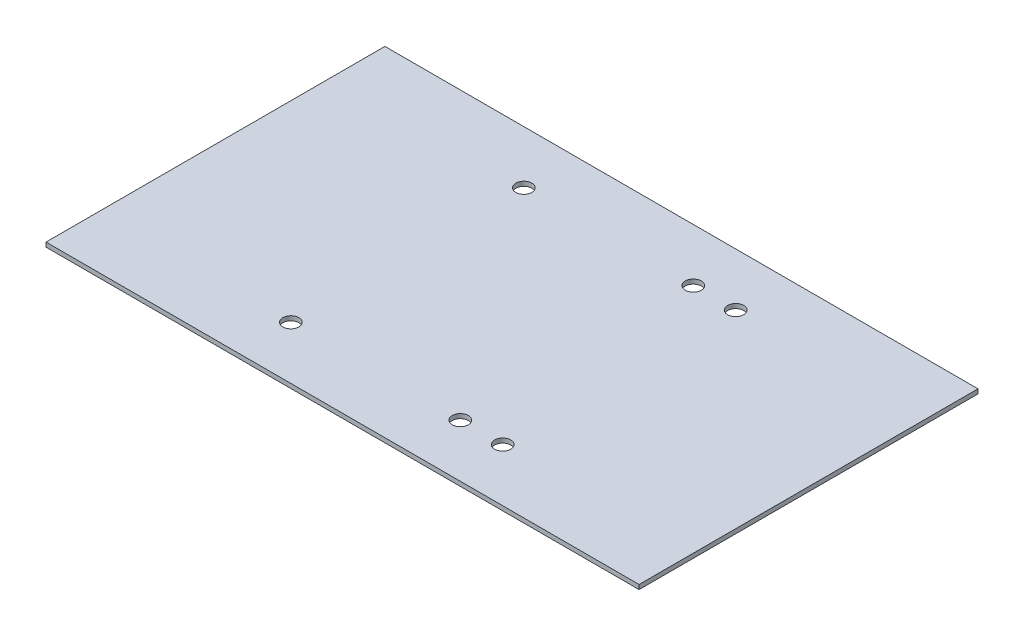
SolidWorks part; units mm, degrees
material "Plain Carbon Steel"
ref_plane "Front Plane" through (0, 0, 0) normal (0, 0, 1) x (1, 0, 0)
ref_plane "Top Plane" through (0, 0, 0) normal (0, 1, 0) x (1, 0, 0)
ref_plane "Right Plane" through (0, 0, 0) normal (1, 0, 0) x (0, 0, -1)
sketch "Sketch1" plane through (0, 0, 0) normal (0, 1, 0) x (1, 0, 0)
  line L1 (0, 0) -> (355.6, 0)
  line L2 (0, 0) -> (0, 203.2)
  line L3 (0, 203.2) -> (355.6, 203.2)
  line L4 (355.6, 0) -> (355.6, 203.2)
  dimension "D1" = 203.2
  dimension "D2" = 355.6
base flange "Base-Flange1" sketch "Sketch1" thickness 2.6568 reverse thickness direction no parameters "D1"=3.175
sketch "Sketch6" plane through (0, 0, 0) normal (0, 1, 0) x (1, 0, 0)
  line L0 (0, 101.6) -> (355.6, 101.6) construction
  line L1 (0, 203.2) -> (0, 0) construction
  line L2 (355.6, 0) -> (355.6, 203.2) construction
  line L3 (177.8, 203.2) -> (177.8, 0) construction
  line L4 (355.6, 203.2) -> (0, 203.2) construction
  line L5 (0, 0) -> (355.6, 0) construction
sketch "Sketch7" plane through (0, -2.6568, 0) normal (0, -1, 0) x (1, 0, 0)
  line L0 (0, -101.6) -> (355.9061, -101.6) construction
  line L1 (0, 0) -> (355.6, 0) construction
  dimension "D1" = 101.6
sketch "Sketch8" plane through (0, 0, 0) normal (0, 1, 0) x (1, 0, 0)
  circle A0 centre (115.062, 171.45) radius 4.826 construction
  circle A1 centre (216.662, 171.45) radius 4.826 construction
  circle A2 centre (242.062, 171.45) radius 4.826 construction
  circle A3 centre (242.062, 31.75) radius 4.826 construction
  circle A4 centre (216.662, 31.75) radius 4.826 construction
  circle A5 centre (115.062, 31.75) radius 4.826 construction
  circle A6 centre (115.062, 171.45) radius 4.826
  circle A7 centre (216.662, 171.45) radius 4.826
  circle A8 centre (242.062, 171.45) radius 4.826
  circle A9 centre (242.062, 31.75) radius 4.826
  circle A10 centre (216.662, 31.75) radius 4.826
  circle A11 centre (115.062, 31.75) radius 4.826
extrude "Cut-Extrude1" cut sketch "Sketch8" against normal through all normal cut yes
sketch "Bend-Lines1" [suppressed] plane through (0, 0, 0) normal (0, 1, 0) x (1, 0, 0)
sketch "Bounding-Box1" [suppressed] plane through (0, 0, 0) normal (0, 1, 0) x (1, 0, 0)
sheet metal parameters "Sheet-Metal1" thickness 2.6568 parameters "D1"=3.175
flat pattern "Flat-Pattern1" [suppressed]
sketch "Bend-Lines2" plane through (0, 0, 0) normal (0, 1, 0) x (1, 0, 0)
sketch3d "Bounding-Box2" [suppressed]
  line L0 (-355.6, 203.2, 0) -> (0, 203.2, 0) construction
  line L1 (-355.6, 0, 0) -> (0, 0, 0) construction
  line L2 (-355.6, 203.2, 0) -> (-355.6, 0, 0) construction
  line L3 (0, 203.2, 0) -> (0, 0, 0) construction
sheet metal parameters "Sheet-Metal2" thickness 2.6568 parameters "D1"=3.175
flat pattern "Flat-Pattern1" [suppressed]
sketch "Bend-Lines2" plane through (0, 0, 0) normal (0, 1, 0) x (1, 0, 0)
sketch3d "Bounding-Box2" [suppressed]
  line L0 (355.6, 203.2, 0) -> (0, 203.2, 0) construction
  line L1 (355.6, 0, 0) -> (0, 0, 0) construction
  line L2 (355.6, 203.2, 0) -> (355.6, 0, 0) construction
  line L3 (0, 203.2, 0) -> (0, 0, 0) construction
sketch "Sketch7-1" plane through (0, -2.6568, 0) normal (0, -1, 0) x (1, 0, 0)
  line L0 (0, -101.6) -> (355.9061, -101.6) construction
  line L1 (0, 0) -> (355.6, 0) construction
  dimension "D1" = 101.6
